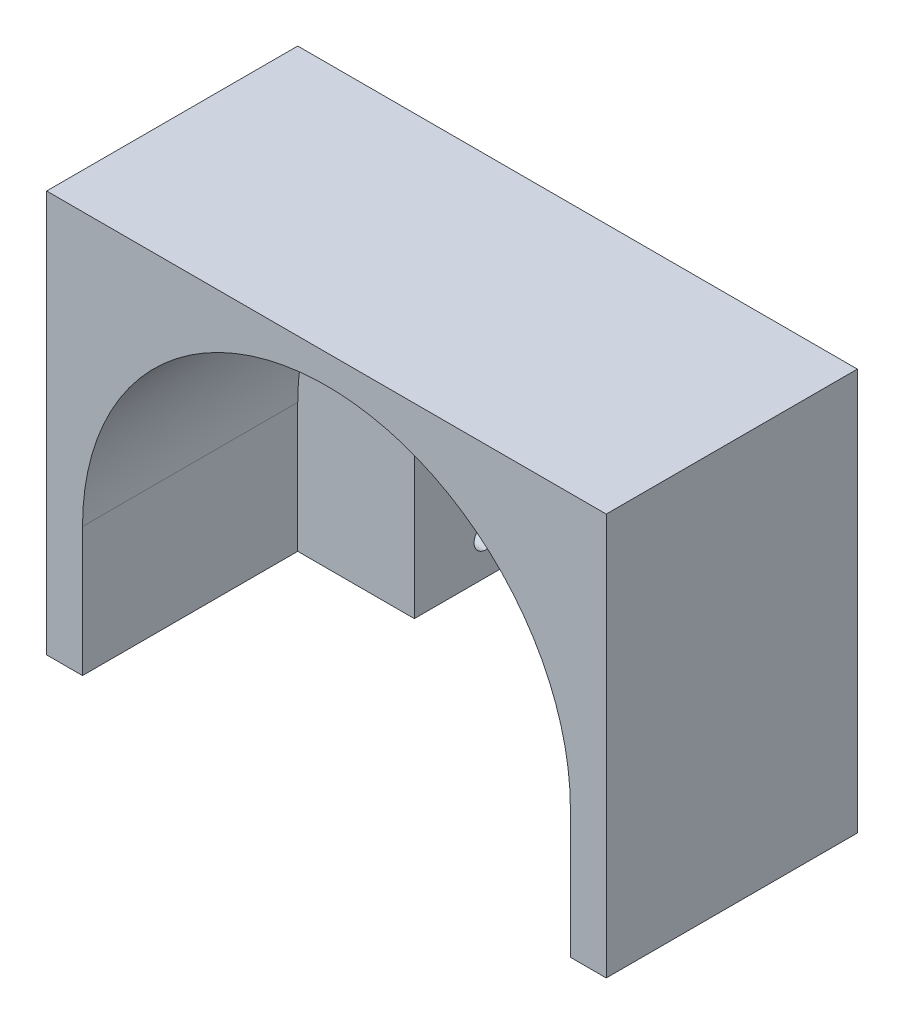
SolidWorks part; units mm, degrees
ref_plane "Plan de face" through (0, 0, 0) normal (0, 0, 1) x (1, 0, 0)
ref_plane "Plan de dessus" through (0, 0, 0) normal (0, 1, 0) x (1, 0, 0)
ref_plane "Plan de droite" through (0, 0, 0) normal (1, 0, 0) x (0, 0, -1)
ref_plane "Plan2" through (0, -10, 0) normal (0, 1, 0) x (1, 0, 0)
sketch "Esquisse3" plane through (0, 0, 0) normal (0, 0, 1) x (1, 0, 0)
  line L1 (-39, 28) -> (39, 28)
  line L2 (-39, 28) -> (-39, -28)
  line L3 (-39, -28) -> (39, -28)
  line L4 (39, 28) -> (39, -28)
  point P4 (0, 28)
  point P5 (-39, 0)
  point P8 (39, 0)
  point P9 (0, -28)
  dimension "D1" = 78
  dimension "D2" = 56
extrude "Boss.-Extru.2" add sketch "Esquisse3" along normal blind 45
sketch "Esquisse4" plane through (0, 0, 45) normal (0, 0, 1) x (1, 0, 0)
  line L2 (39, 28) -> (-39, 28) construction
  line L3 (55, -10) -> (-55, -10) construction
  circle A0 centre (0, -10) radius 34
  point P2 (0, 28)
  dimension "D1" = 68
extrude "Enlèv. mat.-Extru.1" cut sketch "Esquisse4" against normal blind 30
sketch "Esquisse5" plane through (0, 0, 0) normal (0, 0, -1) x (-1, 0, 0)
  line L0 (39, -28) -> (-39, -28) construction
  line L1 (-17.75, 7.5) -> (17.75, 7.5)
  line L2 (-17.75, 7.5) -> (-17.75, -28)
  line L3 (-17.75, -28) -> (17.75, -28)
  line L4 (17.75, 7.5) -> (17.75, -28)
  point P6 (0, -28)
  dimension "D1" = 35.5
  dimension "D2" = 35.5
extrude "Enlèv. mat.-Extru.2" cut sketch "Esquisse5" against normal up to surface (15 mm away) up to face at (0, -2, 15)
sketch "Esquisse8" plane through (0, 0, 0) normal (0, 0, -1) x (-1, 0, 0)
  line L0 (-22.75, -28) -> (-22.75, 12.5)
  line L1 (-17.75, -28) -> (-39, -28) construction
  line L2 (-22.75, 12.5) -> (22.75, 12.5)
  line L3 (22.75, 12.5) -> (22.75, -28)
  line L4 (39, -28) -> (17.75, -28) construction
  line L5 (22.75, -28) -> (39, -28)
  line L6 (39, -28) -> (39, 28)
  line L7 (39, 28) -> (-39, 28)
  line L8 (-39, 28) -> (-39, -28)
  line L9 (-39, -28) -> (-22.75, -28)
  line L10 (17.75, 7.5) -> (-17.75, 7.5) construction
  line L11 (-17.75, 7.5) -> (-17.75, -28) construction
  line L12 (17.75, -28) -> (17.75, 7.5) construction
  dimension "D1" = 5
  dimension "D2" = 5
  dimension "D3" = 5
extrude "Enlèv. mat.-Extru.5" cut sketch "Esquisse8" against normal blind 10
sketch "Esquisse12" plane through (0, 0, 45) normal (0, 0, 1) x (1, 0, 0)
  line L0 (-39, -28) -> (-28.8444, -28) construction
  line L1 (-34, -28) -> (34, -28)
  line L2 (-34, -28) -> (-34, -10)
  line L3 (-34, -10) -> (34, -10)
  line L4 (34, -28) -> (34, -10)
  line L5 (24.75, -10) -> (-24.75, -10) construction
  arc A0 (28.8444, -28) -> (-28.8444, -28) centre (0, -10) ccw construction
extrude "Enlèv. mat.-Extru.6" cut sketch "Esquisse12" against normal up to surface (30 mm away) up to face at (0, -7.5, 15)
sketch "Esquisse13" plane through (-22.75, 0, 0) normal (-1, 0, 0) x (0, 0, 1)
  line L0 (0, 12.5) -> (0, -28) construction
  line L1 (10, -28) -> (0, -28) construction
  circle A0 centre (5, -23) radius 1.6715
  dimension "D1" = 5
  dimension "D2" = 5
extrude "Enlèv. mat.-Extru.7" cut sketch "Esquisse13" against normal through all
sketch "Esquisse15" plane through (-22.75, 0, 0) normal (-1, 0, 0) x (0, 0, 1)
  line L0 (10, 12.5) -> (0, 12.5) construction
  line L1 (0, 12.5) -> (0, -28) construction
  circle A0 centre (5, 2.5) radius 1.5
  dimension "D1" = 3
  dimension "D2" = 10
  dimension "D3" = 5
extrude "Enlèv. mat.-Extru.8" cut sketch "Esquisse15" against normal through all
sketch "Esquisse16" plane through (0, 0, 15) normal (0, 0, 1) x (1, 0, 0)
  line L0 (-17.75, -28) -> (-17.75, 7.5) construction
  line L1 (-21.75, 3.5) -> (-13.75, 3.5)
  line L2 (-21.75, 3.5) -> (-21.75, 11.5)
  line L3 (-21.75, 11.5) -> (-13.75, 11.5)
  line L4 (-13.75, 3.5) -> (-13.75, 11.5)
  line L6 (-17.75, 7.5) -> (17.75, 7.5) construction
  dimension "D1" = 4
  dimension "D2" = 4
  dimension "D3" = 4
  dimension "D4" = 4
extrude "Enlèv. mat.-Extru.9" cut sketch "Esquisse16" against normal blind 4
sketch "Esquisse17" plane through (0, 12.5, 0) normal (0, 1, 0) x (1, 0, 0)
  line L0 (-22.75, -10) -> (-22.75, 0) construction
  line L1 (22.75, 0) -> (-22.75, 0) construction
  circle A0 centre (-12.75, -5) radius 1.5
  dimension "D1" = 3
  dimension "D2" = 10
  dimension "D3" = 5
extrude "Enlèv. mat.-Extru.10" cut sketch "Esquisse17" against normal through all
sketch "Esquisse18" plane through (0, 12.5, 0) normal (0, 1, 0) x (1, 0, 0)
  line L0 (22.75, -10) -> (22.75, 0) construction
  circle A0 centre (12.75, -5) radius 1.5
  dimension "D1" = 3
  dimension "D2" = 5
  dimension "D3" = 10
extrude "Enlèv. mat.-Extru.11" cut sketch "Esquisse18" against normal through all
sketch "Esquisse19" plane through (0, 0, 15) normal (0, 0, 1) x (1, 0, 0)
  line L0 (17.75, 7.5) -> (17.75, -28) construction
  line L1 (13.75, 11.5) -> (21.75, 11.5)
  line L2 (13.75, 11.5) -> (13.75, 3.5)
  line L3 (13.75, 3.5) -> (21.75, 3.5)
  line L4 (21.75, 11.5) -> (21.75, 3.5)
  line L5 (-13.75, 7.5) -> (17.75, 7.5) construction
  dimension "D1" = 4
  dimension "D2" = 4
  dimension "D3" = 4
  dimension "D4" = 4
extrude "Enlèv. mat.-Extru.12" cut sketch "Esquisse19" against normal blind 4
